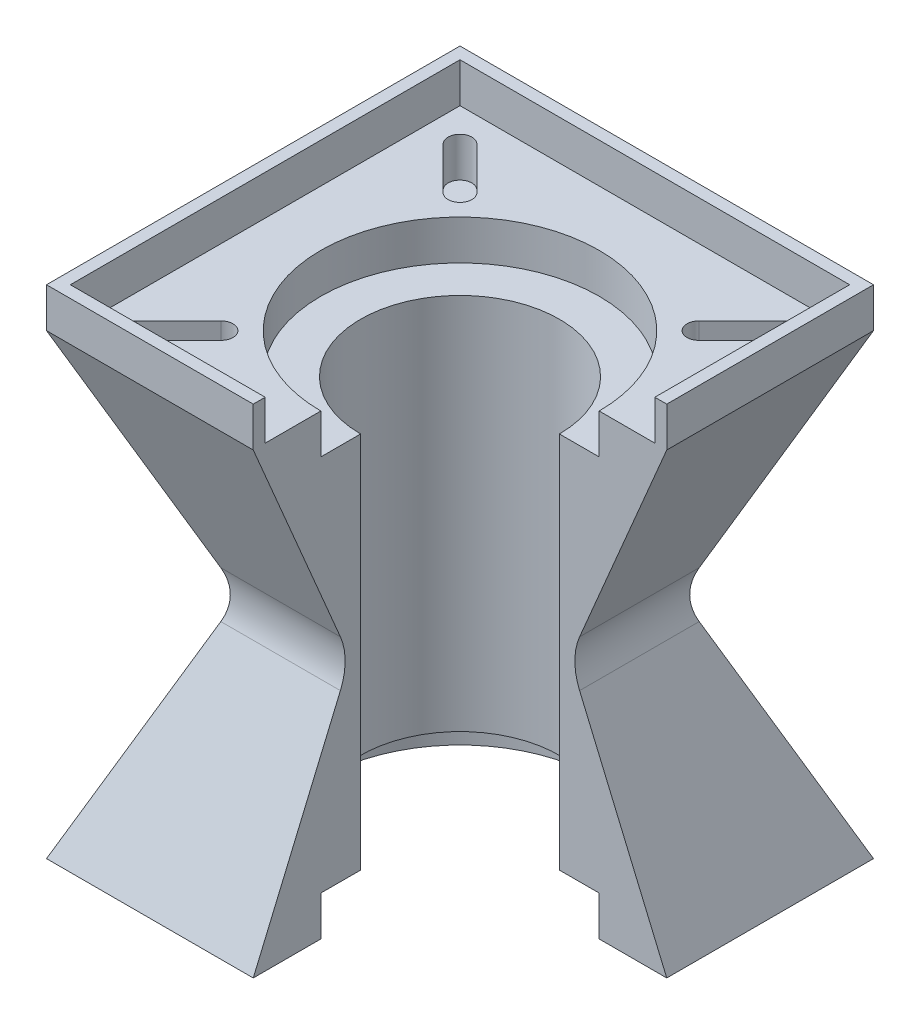
SolidWorks part; units mm, degrees
material "Cast Stainless Steel"
ref_plane "Front Plane" through (0, 0, 0) normal (0, 0, 1) x (1, 0, 0)
ref_plane "Top Plane" through (0, 0, 0) normal (0, 1, 0) x (1, 0, 0)
ref_plane "Right Plane" through (0, 0, 0) normal (1, 0, 0) x (0, 0, -1)
sketch "Sketch1" plane through (0, 0, 0) normal (0, 1, 0) x (1, 0, 0)
  line L1 (-52, 52) -> (52, 52)
  line L2 (-52, 52) -> (-52, -52)
  line L3 (-52, -52) -> (52, -52)
  line L4 (52, 52) -> (52, -52)
  line L5 (-52, 52) -> (52, -52) construction
  line L6 (-52, -52) -> (52, 52) construction
  point P0 (0, 0)
  dimension "D1" = 104
  dimension "D2" = 104
extrude "Boss-Extrude1" add sketch "Sketch1" along normal blind 57.5 draft 23
mirror "Mirror2" about plane through (0, 57.5, 0) normal (0, 1, 0) of bodies 101
sketch "Sketch2" plane through (0, 115, 0) normal (0, 1, 0) x (1, 0, 0)
  circle A0 centre (0, 0) radius 25
  dimension "D1" = 50
extrude "Cut-Extrude1" cut sketch "Sketch2" against normal through all
sketch "Sketch3" plane through (0, 115, 0) normal (0, 1, 0) x (1, 0, 0)
  circle A0 centre (0, 0) radius 35
  dimension "D1" = 70
extrude "Cut-Extrude2" cut sketch "Sketch3" against normal blind 10
ref_plane "Plane2" through (0, 57.5, 0) normal (0, 1, 0) x (1, 0, 0)
mirror "Mirror3" about plane through (0, 57.5, 0) normal (0, 1, 0) of "Cut-Extrude2"
sketch "Sketch4" plane through (0, 115, 0) normal (0, 1, 0) x (1, 0, 0)
  line L0 (52, -52) -> (52, 52) construction
  line L1 (0, 0) -> (52, 0)
  line L2 (0, 0) -> (0, -52)
  line L3 (0, -52) -> (52, -52)
  line L4 (52, 0) -> (52, -52)
extrude "Cut-Extrude3" cut sketch "Sketch4" against normal through all
fillet "Fillet1" radius 15 4 edges at (-13.7963, 57.5, 27.5927) (-27.5927, 57.5, 0) (0, 57.5, -27.5927) (27.5927, 57.5, -13.7963)
sketch "Sketch5" plane through (0, 115, 0) normal (0, 1, 0) x (1, 0, 0)
  line L6 (0, -35) -> (0, -52) construction
  line L7 (52, 0) -> (35, 0) construction
  line L8 (49, 0) -> (52, 0)
  line L9 (52, 0) -> (52, 52)
  line L10 (52, 52) -> (-52, 52)
  line L11 (-52, 52) -> (-52, -52)
  line L12 (-49, -49) -> (-3, -49)
  line L13 (-3, -49) -> (-3, -37.8814)
  line L14 (37.8814, 3) -> (49, 3)
  line L15 (49, 3) -> (49, 49)
  line L16 (49, 49) -> (-49, 49)
  line L17 (-49, 49) -> (-49, -49)
  line L18 (-49, -49) -> (0, -49)
  line L21 (49, 0) -> (49, 49)
  line L22 (49, 49) -> (-49, 49)
  line L23 (-49, 49) -> (-49, -49)
  line L24 (-52, -52) -> (0, -52)
  line L25 (0, -52) -> (0, -49)
  arc A2 (37.8814, 3) -> (-3, -37.8814) centre (0, 0) ccw
  dimension "D1" = 3
extrude "Boss-Extrude2" add sketch "Sketch5" along normal blind 10
sketch "Sketch6" plane through (0, 115, 0) normal (0, 1, 0) x (1, 0, 0)
  line L0 (0, 0) -> (-49, 49) construction
  line L1 (-40.6586, 40.6586) -> (-30.052, 30.052) construction
  line L2 (-38.5373, 42.78) -> (-27.9307, 32.1734)
  line L3 (-42.78, 38.5373) -> (-32.1734, 27.9307)
  line L4 (40.6586, 40.6586) -> (30.052, 30.052) construction
  line L5 (42.78, 38.5373) -> (32.1734, 27.9307)
  line L6 (38.5373, 42.78) -> (27.9307, 32.1734)
  line L10 (-40.6586, -40.6586) -> (-30.052, -30.052) construction
  line L11 (-42.78, -38.5373) -> (-32.1734, -27.9307)
  line L12 (-38.5373, -42.78) -> (-27.9307, -32.1734)
  line L16 (40.6586, -40.6586) -> (30.052, -30.052) construction
  line L17 (38.5373, -42.78) -> (27.9307, -32.1734)
  line L18 (42.78, -38.5373) -> (32.1734, -27.9307)
  line L19 (40.6586, -40.6586) -> (30.052, -30.052) construction
  line L20 (38.5373, -42.78) -> (27.9307, -32.1734)
  line L21 (42.78, -38.5373) -> (32.1734, -27.9307)
  arc A0 (-38.5373, 42.78) -> (-42.78, 38.5373) centre (-40.6586, 40.6586) ccw
  arc A1 (-32.1734, 27.9307) -> (-27.9307, 32.1734) centre (-30.052, 30.052) ccw
  arc A2 (42.78, 38.5373) -> (38.5373, 42.78) centre (40.6586, 40.6586) ccw
  arc A3 (27.9307, 32.1734) -> (32.1734, 27.9307) centre (30.052, 30.052) ccw
  arc A6 (-42.78, -38.5373) -> (-38.5373, -42.78) centre (-40.6586, -40.6586) ccw
  arc A7 (-27.9307, -32.1734) -> (-32.1734, -27.9307) centre (-30.052, -30.052) ccw
  arc A12 (38.5373, -42.78) -> (42.78, -38.5373) centre (40.6586, -40.6586) ccw
  arc A13 (32.1734, -27.9307) -> (27.9307, -32.1734) centre (30.052, -30.052) ccw
  point P6 (-35.3553, 35.3553)
  point P13 (35.3553, -35.3553)
  point P16 (35.3553, 35.3553)
  point P21 (0, 0)
  point P30 (-35.3553, -35.3553)
  point P35 (0, 0)
  point P42 (35.3553, -35.3553)
  point P49 (35.3553, -35.3553)
  dimension "D2" = 3
  dimension "D1" = 15
  dimension "D3" = 50
  dimension "D4" = 4
extrude "Cut-Extrude4" cut sketch "Sketch6" against normal blind 10
equation "\"a\"= 115mm"
equation "\"b\"= 104mm"
equation "\"c\"= 23mm"
